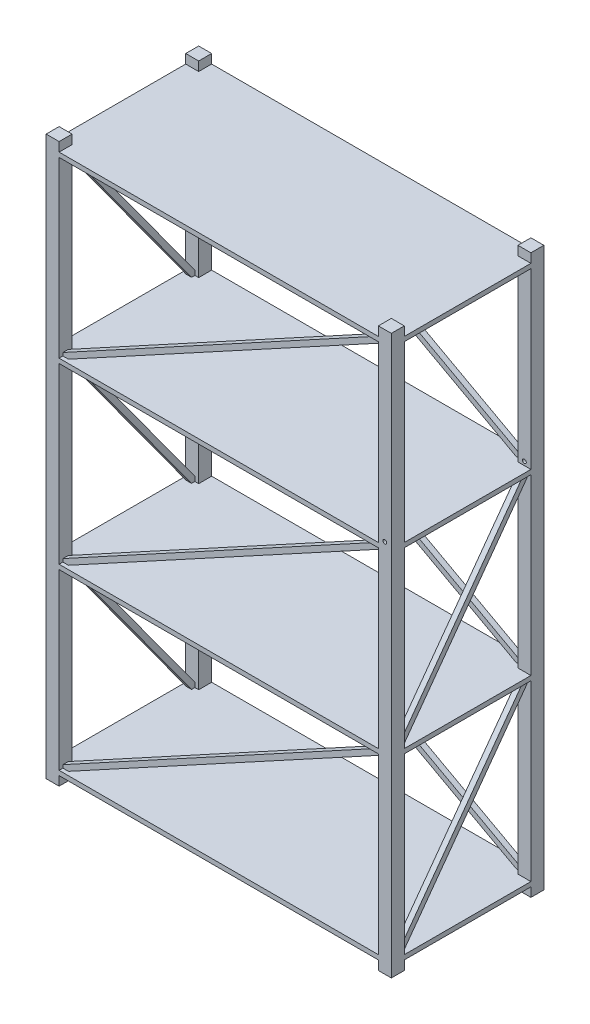
SolidWorks part; units mm, degrees
material "5052-H36"
ref_plane "Front Plane" through (0, 0, 0) normal (0, 0, 1) x (1, 0, 0)
ref_plane "Top Plane" through (0, 0, 0) normal (0, 1, 0) x (1, 0, 0)
ref_plane "Right Plane" through (0, 0, 0) normal (1, 0, 0) x (0, 0, -1)
sketch "Sketch2" plane through (0, 0, 0) normal (0, 1, 0) x (1, 0, 0)
  line L1 (-113.15, -50) -> (113.15, -50)
  line L2 (-113.15, -50) -> (-113.15, 50)
  line L3 (-113.15, 50) -> (113.15, 50)
  line L4 (113.15, -50) -> (113.15, 50)
  line L5 (-113.15, -50) -> (113.15, 50) construction
  line L6 (-113.15, 50) -> (113.15, -50) construction
  point P0 (0, 0)
  dimension "D1" = 226.3
  dimension "D2" = 100
extrude "Boss-Extrude1" add sketch "Sketch2" along normal mid plane 366
sketch "Sketch4" plane through (0, -183, 0) normal (0, -1, 0) x (1, 0, 0)
  line L5 (-113.15, 50) -> (-104.65, 50)
  line L6 (-113.15, 50) -> (-113.15, 41.5)
  line L7 (-113.15, 41.5) -> (-104.65, 41.5)
  line L8 (-104.65, 50) -> (-104.65, 41.5)
  line L9 (-113.15, -50) -> (-104.65, -50)
  line L10 (-113.15, -50) -> (-113.15, -41.5)
  line L11 (-113.15, -41.5) -> (-104.65, -41.5)
  line L16 (-104.65, -50) -> (-104.65, -41.5)
  line L17 (113.15, -50) -> (104.65, -50)
  line L18 (113.15, -50) -> (113.15, -41.5)
  line L19 (113.15, -41.5) -> (104.65, -41.5)
  line L20 (104.65, -50) -> (104.65, -41.5)
  line L21 (113.15, 50) -> (104.65, 50)
  line L22 (113.15, 50) -> (113.15, 41.5)
  line L23 (113.15, 41.5) -> (104.65, 41.5)
  line L24 (104.65, 50) -> (104.65, 41.5)
  dimension "D1" = 8.5
extrude "Cut-Extrude1" cut sketch "Sketch4" against normal blind 6 flip side to cut
mirror "Mirror1" about plane through (0, 0, 0) normal (0, 1, 0) of "Cut-Extrude1"
sketch "Sketch5" plane through (0, 0, 50) normal (0, 0, 1) x (1, 0, 0)
  line L0 (-104.65, -177) -> (-104.65, -183) construction
  line L1 (-104.65, 174) -> (104.65, 174)
  line L2 (-104.65, 174) -> (-104.65, 60)
  line L3 (-104.65, -174) -> (104.65, -174)
  line L4 (104.65, 174) -> (104.65, 60)
  line L5 (104.65, -177) -> (104.65, -183) construction
  line L6 (104.65, -177) -> (-104.65, -177) construction
  line L7 (-104.65, 177) -> (104.65, 177) construction
  line L8 (-104.65, 60) -> (104.65, 60)
  line L9 (-104.65, 57) -> (-104.65, -57)
  line L10 (104.65, 57) -> (-104.65, 57)
  line L12 (-104.65, -57) -> (104.65, -57)
  line L13 (104.65, 57) -> (104.65, -57)
  line L14 (104.65, -60) -> (-104.65, -60)
  line L15 (104.65, -60) -> (104.65, -174)
  line L16 (-104.65, -60) -> (-104.65, -174)
  line L17 (-104.65, 60) -> (-104.65, 57) construction
  line L18 (-104.65, -57) -> (-104.65, -60) construction
  line L19 (-104.65, -174) -> (-104.65, -177) construction
  dimension "D1" = 3
  dimension "D2" = 3
extrude "Cut-Extrude2" cut sketch "Sketch5" against normal through all
sketch "Sketch6" plane through (113.15, 0, 0) normal (1, 0, 0) x (0, 0, -1)
  line L8 (-41.5, 174) -> (-41.5, 60)
  line L9 (41.5, -174) -> (41.5, -60)
  line L10 (-41.5, 57) -> (-41.5, -57)
  line L11 (41.5, 60) -> (41.5, 174)
  line L12 (-50, 174) -> (-50, 60)
  line L13 (-50, 60) -> (50, 60)
  line L14 (50, 60) -> (50, 174)
  line L15 (50, 174) -> (-50, 174)
  line L17 (-41.5, 60) -> (41.5, 60)
  line L19 (41.5, 174) -> (-41.5, 174)
  line L20 (-50, 57) -> (-50, -57)
  line L21 (-50, -57) -> (50, -57)
  line L22 (50, -57) -> (50, 57)
  line L23 (50, 57) -> (-50, 57)
  line L25 (-41.5, -57) -> (41.5, -57)
  line L27 (41.5, 57) -> (-41.5, 57)
  line L28 (-50, -60) -> (-50, -174)
  line L29 (-50, -174) -> (50, -174)
  line L30 (50, -174) -> (50, -60)
  line L31 (50, -60) -> (-50, -60)
  line L33 (-41.5, -174) -> (41.5, -174)
  line L35 (41.5, -60) -> (-41.5, -60)
  line L36 (41.5, -57) -> (41.5, 57)
  line L37 (-41.5, -60) -> (-41.5, -174)
  line L38 (-41.5, -177) -> (-41.5, -183) construction
  line L39 (41.5, -177) -> (41.5, -183) construction
  dimension "D1" = 0
  dimension "D2" = 0
  dimension "D3" = 0
extrude "Cut-Extrude3" cut sketch "Sketch6" against normal through all
sketch "Sketch7" plane through (0, 0, 50) normal (0, 0, 1) x (1, 0, 0)
  line L0 (-104.65, -174) -> (104.65, -60)
  line L1 (-104.65, -57) -> (104.65, 57)
  line L2 (-104.65, 60) -> (104.65, 174)
extrude "Extrude-Thin1" add sketch "Sketch7" against normal blind 3.5 from offset 2.5 thin offset against normal yes thin type mid plane wall 3.5
sketch "Sketch8" plane through (113.15, 0, 0) normal (1, 0, 0) x (0, 0, -1)
  line L0 (-41.5, -174) -> (41.5, -60)
  line L1 (-41.5, -57) -> (41.5, 57)
  line L2 (-41.5, 60) -> (41.5, 174)
extrude "Extrude-Thin2" add sketch "Sketch8" against normal blind 3.5 from offset 2.5 thin offset against normal yes thin type mid plane wall 3.5
ref_axis "Axis1" through (0, -201.3, 0) along (0, 1, 0)
pattern_circular "CirPattern1" count 2 over 360 about axis through (0, -201.3, 0) along (0, 1, 0) of "Extrude-Thin1", "Extrude-Thin2"
other "DeleteFace2" face at (110.65, 117, 0) face at (108.9, 115.5134, -1.0823) face at (108.9, 118.4866, 1.0823) face at (107.15, 117, 0) and patch yes
sketch "Sketch9" plane through (0, 0, 0) normal (0, 0, 1) x (1, 0, 0)
  line L0 (113.15, 183) -> (113.15, -183) construction
  line L2 (-104.65, 60) -> (104.65, 60) construction
  circle A0 centre (108.9, 62.5) radius 1.25
  dimension "D3" = 2.5
  dimension "D1" = 4.25
  dimension "D2" = 2.5
extrude "Cut-Extrude4" cut sketch "Sketch9" against normal through all both and the other way through all
